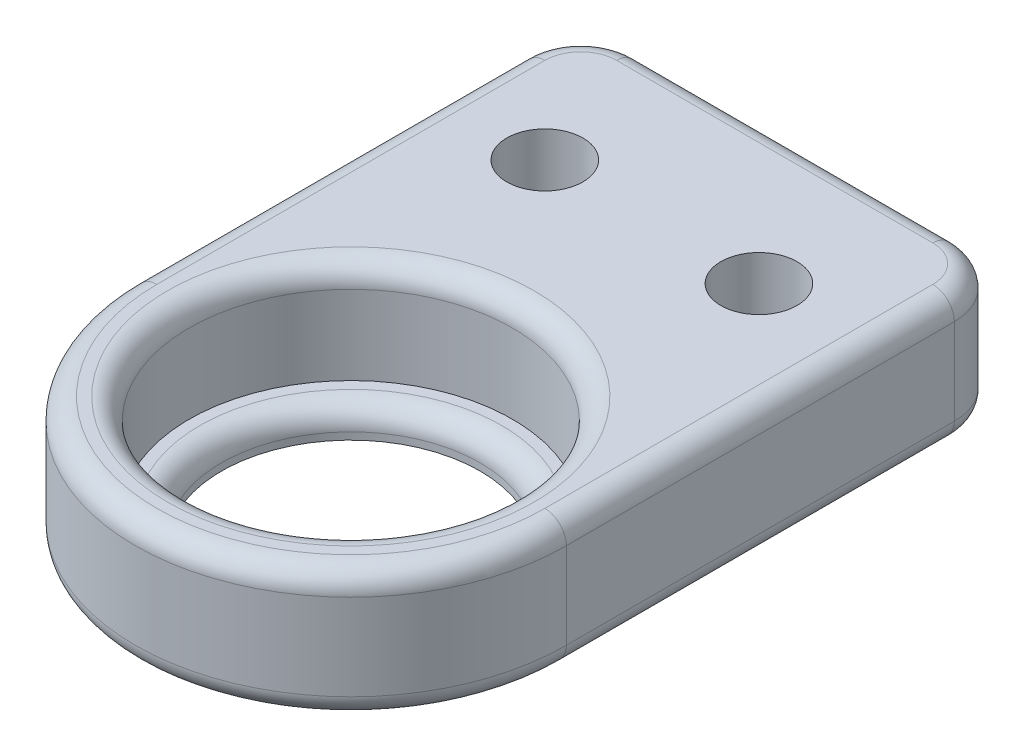
SolidWorks part; units mm, degrees
ref_plane "Front Plane" through (0, 0, 0) normal (0, 0, 1) x (1, 0, 0)
ref_plane "Top Plane" through (0, 0, 0) normal (0, 1, 0) x (1, 0, 0)
ref_plane "Right Plane" through (0, 0, 0) normal (1, 0, 0) x (0, 0, -1)
sketch "Sketch2" plane through (0, 0, 0) normal (0, 1, 0) x (1, 0, 0)
  line L1 (-15, 0) -> (15, 0)
  line L2 (-15, 0) -> (-15, 31)
  line L3 (-15, 31) -> (15, 31)
  line L4 (15, 0) -> (15, 31)
  circle A0 centre (0, 0) radius 11.25
  arc A1 (15, 0) -> (-15, 0) centre (0, 0) cw
  circle A2 centre (0, 0) radius 9
  point P8 (11.25, 0)
  point P9 (-11.25, 0)
  point P11 (0, 11.25)
  dimension "D1" = 22.5
  dimension "D2" = 18
  dimension "D4" = 31
  dimension "30" = 30
extrude "Boss-Extrude1" add sketch "Sketch2" along normal blind 9 contours A1 L1 A0 | A0 L1 L4 L3 L2 region at (0, 0, -18.4161) region at (13.125, 0, 0.3354)
extrude "Boss-Extrude2" add sketch "Sketch2<3>" along normal blind 2 contours A2 L1 A0 | A2 L1 A0 region at (0, 0, -9.2516) region at (10.125, 0, 0.2516)
sketch "Sketch2<3>" plane through (0, 0, 0) normal (0, 1, 0) x (1, 0, 0) same geometry as "Sketch2"
hole_wizard "CSK for M5 SFHCS1" positions "3DSketch2" profile "Sketch3" countersink size "M5" standard "ANSI Metric" end condition through all
sketch3d "3DSketch2"
  line L0 (15, 0, 0) -> (15, 0, -31) construction
  line L1 (-15, 0, -31) -> (15, 0, -31) construction
  line L2 (-15, 0, 0) -> (-15, 0, -31) construction
  point P0 (7.4, 0, -21)
  point P2 (-7.5, 0, -21)
  dimension "D1" = 7.6
  dimension "D2" = 10
  dimension "D3" = 10
  dimension "D4" = 7.5
sketch "Sketch3" plane through (7.4, 0, -21) normal (1, 0, 0) x (0, 0, -1)
  line L0 (0, 0) -> (0, 9)
  line L1 (0, 9) -> (2.65, 9)
  line L2 (2.65, 9) -> (2.65, 2.95)
  line L3 (2.65, 2.95) -> (5.6, 0)
  line L5 (5.6, 0) -> (0, 0)
  line L6 (-2.65, 2.95) -> (-5.6, 0) construction
  line L11 (0, -6.35) -> (0, 107.95) construction
  dimension "Thru Hole Dia." = 5.3
  dimension "Thru Hole Depth" = 9
  dimension "Near C'Sink Dia." = 11.2
  dimension "Near C'Sink Angle" = 90
fillet "Fillet1" radius 4 2 edges at (-15, 4.5, -31) (15, 4.5, -31)
fillet "Fillet2" radius 1.5 14 edges at (0, 0, 15) (-15, 0, -13.5) (-13.8284, 0, -29.8284) (0, 0, -31) (13.8284, 0, -29.8284) (0, 9, 15) (-15, 9, -13.5) (-13.8284, 9, -29.8284) (0, 9, -31) (13.8284, 9, -29.8284) (0, 2, 9) (0, 9, 11.25) (15, 0, -13.5) (15, 9, -13.5)
